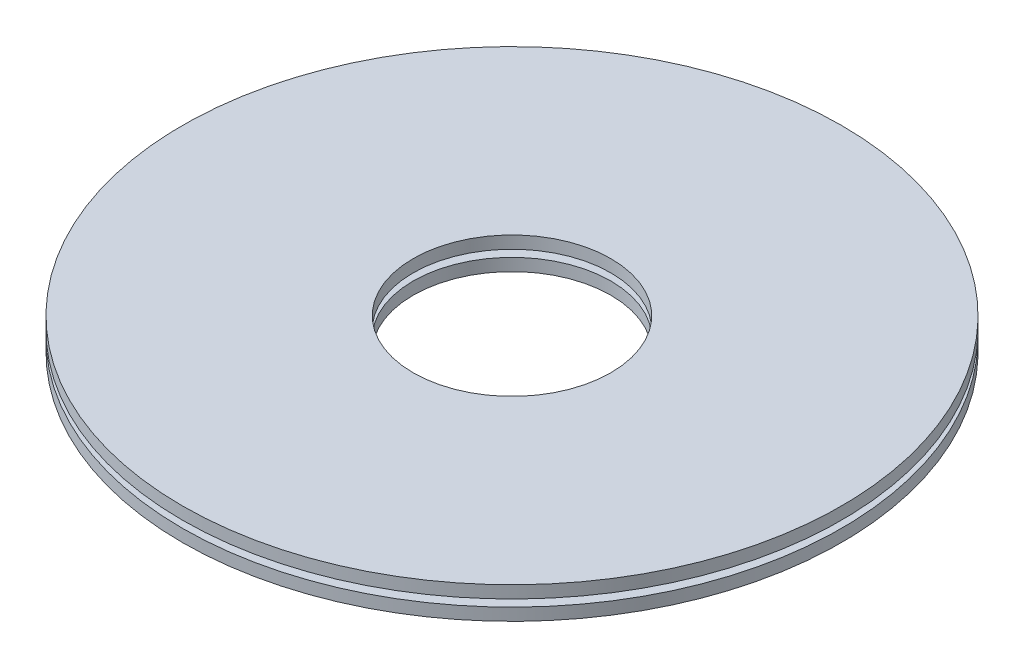
SolidWorks part; units mm, degrees
ref_plane "Front Plane" through (0, 0, 0) normal (0, 0, 1) x (1, 0, 0)
ref_plane "Top Plane" through (0, 0, 0) normal (0, 1, 0) x (1, 0, 0)
ref_plane "Right Plane" through (0, 0, 0) normal (1, 0, 0) x (0, 0, -1)
sketch "Sketch1" plane through (0, 0, 0) normal (0, 1, 0) x (1, 0, 0)
  circle A0 centre (0, 0) radius 762
extrude "bottomTable" add sketch "Sketch1" along normal blind 28.575
ref_plane "Plane1" through (0, 44.831, 0) normal (0, 1, 0) x (1, 0, 0)
sketch "Sketch2" plane through (0, 44.831, 0) normal (0, 1, 0) x (1, 0, 0)
  circle A0 centre (0, 0) radius 762
extrude "topTable" add sketch "Sketch2" along normal blind 28.575 separate body
sketch "Sketch3" plane through (0, 73.406, 0) normal (0, 1, 0) x (1, 0, 0)
  circle A0 centre (0, 0) radius 228.6
extrude "Cut-Extrude1" cut sketch "Sketch3" against normal up to surface (73.406 mm away) up to face at (0, 0, 762)
ref_axis "tableAxis" through (0, 77.0763, 0) along (0, -1, 0)
